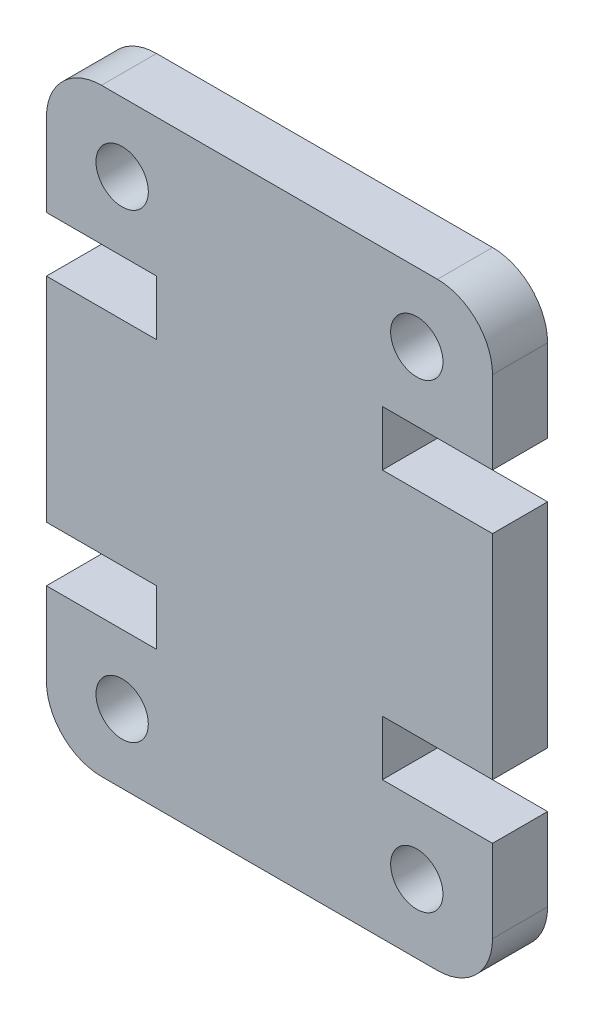
SolidWorks part; units mm, degrees
ref_plane "Front Plane" through (0, 0, 0) normal (0, 0, 1) x (1, 0, 0)
ref_plane "Top Plane" through (0, 0, 0) normal (0, 1, 0) x (1, 0, 0)
ref_plane "Right Plane" through (0, 0, 0) normal (1, 0, 0) x (0, 0, -1)
sketch "Sketch1" plane through (0, 0, 0) normal (0, 0, 1) x (1, 0, 0)
  line L0 (0, 14.74) -> (0, 7)
  line L1 (16.2, 2) -> (16.2, 5)
  line L2 (12.2, 5) -> (16.2, 5)
  line L3 (2, 0) -> (14.2, 0)
  line L4 (16.2, 7) -> (12.2, 7)
  line L5 (12.2, 7) -> (12.2, 5)
  line L6 (16.2, 14.74) -> (16.2, 7)
  line L7 (4, 7) -> (4, 5)
  line L8 (0, 19.74) -> (0, 16.74)
  line L9 (4, 16.74) -> (0, 16.74)
  line L10 (0, 7) -> (4, 7)
  line L11 (0, 14.74) -> (4, 14.74)
  line L12 (4, 5) -> (0, 5)
  line L13 (4, 14.74) -> (4, 16.74)
  line L14 (12.2, 14.74) -> (12.2, 16.74)
  line L15 (16.2, 14.74) -> (12.2, 14.74)
  line L16 (0, 2) -> (0, 5)
  line L17 (2, 21.74) -> (14.2, 21.74)
  line L18 (12.2, 16.74) -> (16.2, 16.74)
  line L19 (16.2, 19.74) -> (16.2, 16.74)
  line L20 (8.1, 21.74) -> (8.1, 0) construction
  line L21 (0, 10.87) -> (16.2, 10.87) construction
  circle A0 centre (13.45, 2.5) radius 0.95
  arc A1 (16.2, 2) -> (14.2, 0) centre (14.2, 2) cw
  circle A2 centre (2.75, 19.24) radius 0.95
  arc A3 (0, 2) -> (2, 0) centre (2, 2) ccw
  arc A4 (0, 19.74) -> (2, 21.74) centre (2, 19.74) cw
  circle A5 centre (2.75, 2.5) radius 0.95
  arc A6 (16.2, 19.74) -> (14.2, 21.74) centre (14.2, 19.74) ccw
  circle A7 centre (13.45, 19.24) radius 0.95
  point P15 (8.1, 10.87)
  dimension "D1" = 1.9
  dimension "D2" = 2
  dimension "D3" = 2.75
  dimension "D4" = 8.1
  dimension "D5" = 2.5
  dimension "D8" = 10.87
  dimension "D6" = 5
extrude "Boss-Extrude1" add sketch "Sketch1" along normal blind 4
sketch "Sketch2" plane through (0, 0, 0) normal (0, 0, -1) x (-1, 0, 0)
  line L0 (0, 0) -> (-16.2, 0)
  line L1 (-16.2, 0) -> (-16.2, 21.74)
  line L2 (-16.2, 21.74) -> (0, 21.74)
  line L3 (0, 21.74) -> (0, 0)
extrude "Cut-Extrude1" cut sketch "Sketch2" against normal blind 2
equation "\"D4@Sketch1\"= \"fingerWidth@parametersSketch@prostheticParameters.SLDPRT\" / 2'PIP width"
equation "\"D8@Sketch1\"= ( \"HL@parametersSketch@prostheticParameters.SLDPRT\" * 0.204 - 4 - 12 ) / 2 'PIP length - Sil. Sht MIP - Sil.Sht PIP"
equation "\"D1@Sketch1\"= 1.5 + \"tol1@parametersSketch@prostheticParameters.SLDPRT\""
